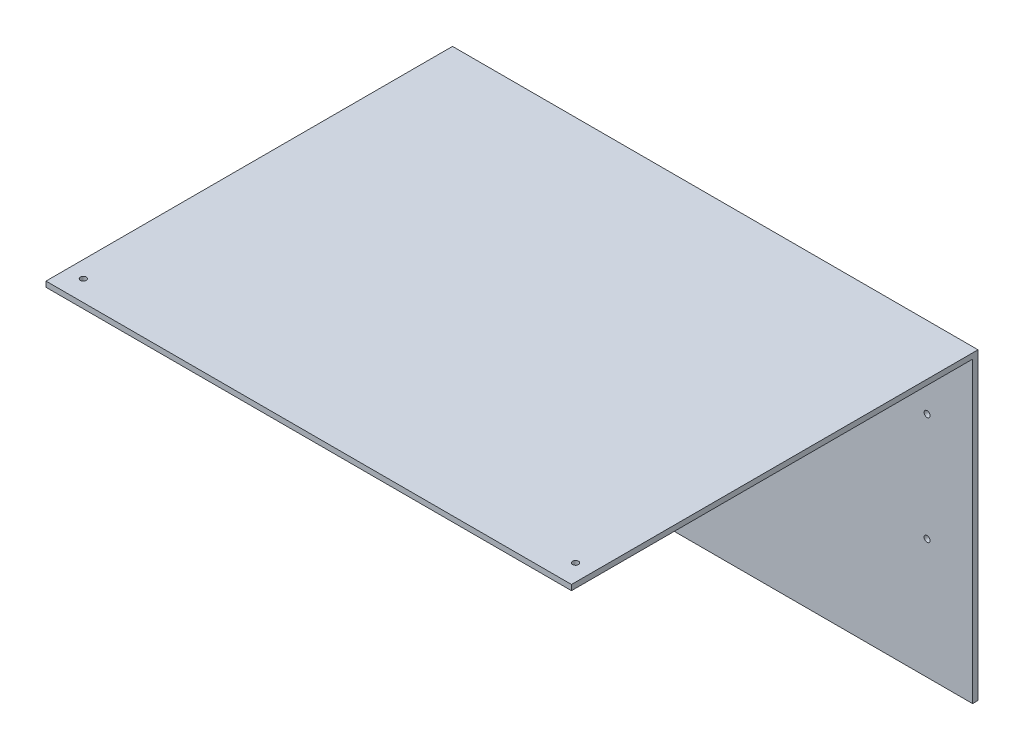
SolidWorks part; units mm, degrees
material "Ti-5Al-2.5Sn Annealed (SS)"
ref_plane "Front Plane" through (0, 0, 0) normal (0, 0, 1) x (1, 0, 0)
ref_plane "Top Plane" through (0, 0, 0) normal (0, 1, 0) x (1, 0, 0)
ref_plane "Right Plane" through (0, 0, 0) normal (1, 0, 0) x (0, 0, -1)
sketch "Sketch1" plane through (0, 0, 0) normal (0, 0, 1) x (1, 0, 0)
  line L1 (0, 0) -> (291.5, 0)
  line L2 (0, 0) -> (0, -168.5)
  line L3 (0, -168.5) -> (291.5, -168.5)
  line L4 (291.5, 0) -> (291.5, -168.5)
  dimension "D1" = 291.5
  dimension "D2" = 168.5
extrude "Boss-Extrude1" add sketch "Sketch1" along normal blind 3
sketch "Sketch2" plane through (0, 0, 3) normal (0, 0, 1) x (1, 0, 0)
  line L0 (145.75, 0) -> (145.75, -168.5) construction
  line L1 (291.5, 0) -> (0, 0) construction
  line L2 (0, -168.5) -> (291.5, -168.5) construction
  point P6 (25.25, -42)
  point P7 (25.25, -102)
  point P11 (266.25, -102)
  point P12 (266.25, -42)
  dimension "D1" = 120.5
  dimension "D2" = 42
  dimension "D3" = 60
hole_wizard "Tap Drill for M4 Tap1" positions "Sketch3" profile "Sketch4" hole size "M4" standard "ISO" end condition up to next
sketch "Sketch3" plane through (0, 0, 3) normal (0, 0, 1) x (1, 0, 0)
  point P0 (25.25, -102)
  point P3 (25.25, -42)
  point P6 (266.25, -42)
  point P9 (266.25, -102)
sketch "Sketch4" plane through (25.25, -102, 3) normal (1, 0, 0) x (0, -1, 0)
  line L0 (0, 0) -> (0, 3)
  line L1 (0, 3) -> (1.65, 3)
  line L2 (1.65, 3) -> (1.65, 0)
  line L5 (1.65, 0) -> (0, 0)
  line L11 (0, -6.35) -> (0, 107.95) construction
  dimension "Thru Hole Dia." = 3.3
  dimension "Thru Hole Depth" = 3
sketch "Sketch6" plane through (0, 0, 3) normal (0, 0, 1) x (1, 0, 0)
  line L0 (291.5, -168.5) -> (291.5, 0) construction
  line L1 (0, 0) -> (291.5, 0)
  line L2 (0, 0) -> (0, -3)
  line L3 (0, -3) -> (291.5, -3)
  line L4 (291.5, 0) -> (291.5, -3)
  dimension "D1" = 3
extrude "Boss-Extrude2" add sketch "Sketch6" along normal blind 222.5
sketch "Sketch7" plane through (0, 0, 0) normal (0, 1, 0) x (1, 0, 0)
  line L0 (145.75, 0) -> (145.75, -225.5) construction
  line L1 (291.5, 0) -> (0, 0) construction
  line L2 (291.5, -225.5) -> (0, -225.5) construction
  point P0 (9.25, -214)
  point P7 (282.25, -214)
  dimension "D1" = 136.5
  dimension "D2" = 11.5
hole_wizard "Tap Drill for M4 Tap2" positions "Sketch7" profile "Sketch8" hole size "M4" standard "ISO" end condition up to next
sketch "Sketch8" plane through (9.25, 0, 214) normal (1, 0, 0) x (0, 0, 1)
  line L0 (0, 0) -> (0, 3)
  line L1 (0, 3) -> (1.65, 3)
  line L2 (1.65, 3) -> (1.65, 0)
  line L5 (1.65, 0) -> (0, 0)
  line L11 (0, -6.35) -> (0, 107.95) construction
  dimension "Thru Hole Dia." = 3.3
  dimension "Thru Hole Depth" = 3
